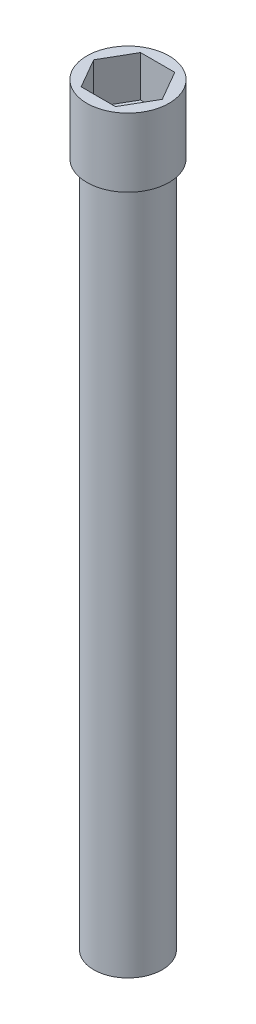
SolidWorks part; units mm, degrees
ref_plane "Front Plane" through (0, 0, 0) normal (0, 0, 1) x (1, 0, 0)
ref_plane "Top Plane" through (0, 0, 0) normal (0, 1, 0) x (1, 0, 0)
ref_plane "Right Plane" through (0, 0, 0) normal (1, 0, 0) x (0, 0, -1)
sketch "Sketch1" plane through (0, 0, 0) normal (0, 1, 0) x (1, 0, 0)
  circle A0 centre (0, 0) radius 12.5
  dimension "D1" = 25
extrude "Boss-Extrude1" add sketch "Sketch1" along normal blind 250
sketch "Sketch2" plane through (0, 250, 0) normal (0, 1, 0) x (1, 0, 0)
  circle A0 centre (0, 0) radius 15
  dimension "D1" = 30
extrude "Boss-Extrude2" add sketch "Sketch2" along normal blind 25
sketch "Sketch3" plane through (0, 275, 0) normal (0, 1, 0) x (1, 0, 0)
  line L1 (-12.5, 0) -> (-6.25, -10.8253)
  line L2 (-6.25, -10.8253) -> (6.25, -10.8253)
  line L3 (6.25, -10.8253) -> (12.5, 0)
  line L4 (12.5, 0) -> (6.25, 10.8253)
  line L5 (6.25, 10.8253) -> (-6.25, 10.8253)
  line L6 (-6.25, 10.8253) -> (-12.5, 0)
  circle A0 centre (0, 0) radius 12.5 construction
  dimension "D1" = 25
extrude "Cut-Extrude1" cut sketch "Sketch3" against normal blind 15
